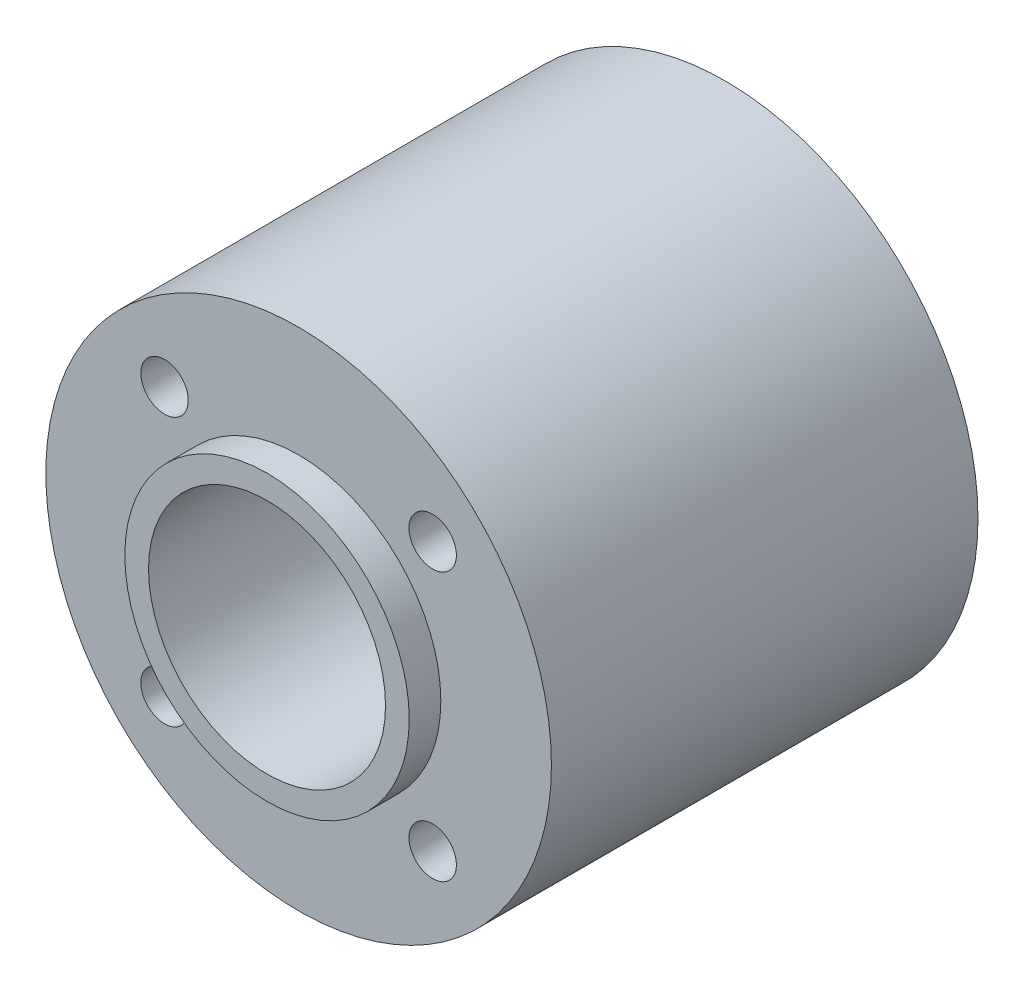
SolidWorks part; units mm, degrees
ref_plane "Plan de face" through (0, 0, 0) normal (0, 0, 1) x (1, 0, 0)
ref_plane "Plan de dessus" through (0, 0, 0) normal (0, 1, 0) x (1, 0, 0)
ref_plane "Plan de droite" through (0, 0, 0) normal (1, 0, 0) x (0, 0, -1)
sketch "Esquisse3" plane through (0, 0, 0) normal (0, 0, 1) x (1, 0, 0)
  circle A0 centre (0, 0) radius 7.5
  circle A1 centre (0, 0) radius 9
  circle A2 centre (0, 0) radius 16
  dimension "D1" = 32
  dimension "D2" = 18
  dimension "D3" = 15
extrude "Boss.-Extru.1" add sketch "Esquisse3" against normal blind 27 contours A2 A1 region at (-15.5475, 0, 0)
extrude "Boss.-Extru.2" add sketch "Esquisse3<3>" along normal blind 2 separate body contours A1 A0 region at (-8.7454, 0, 0)
sketch "Esquisse3<3>" plane through (0, 0, 0) normal (0, 0, 1) x (1, 0, 0) same geometry as "Esquisse3"
sketch "Esquisse5" plane through (0, 0, 2) normal (0, 0, 1) x (1, 0, 0)
  circle A0 centre (0, 0) radius 7.5 construction
  circle A1 centre (0, 0) radius 9
  circle A2 centre (0, 0) radius 9
  circle A3 centre (0, 0) radius 7.5
  dimension "D1" = 0
sketch "Esquisse7" plane through (0, 0, 0) normal (0, 0, -1) x (-1, 0, 0)
  circle A0 centre (0, 0) radius 7.5 construction
  circle A1 centre (0, 0) radius 9
  circle A2 centre (0, 0) radius 9
  circle A3 centre (0, 0) radius 7.5
  dimension "D1" = 0
extrude "Boss.-Extru.3" add sketch "Esquisse7" along normal blind 30
sketch "Esquisse8" plane through (0, 0, 0) normal (0, 0, 1) x (1, 0, 0)
  line L0 (0, 15.2709) -> (0, 0) construction
  line L1 (0, 0) -> (-12.0191, 12.0191) construction
  circle A0 centre (0, 0) radius 12 construction
  circle A1 centre (-8.4853, 8.4853) radius 1.5
  circle A2 centre (8.4853, 8.4853) radius 1.5
  dimension "D2" = 24
  dimension "D3" = 3
  dimension "D1" = 45
extrude "Enlèv. mat.-Extru.1" cut sketch "Esquisse8" against normal blind 30 contours A1 | A2 region at (-8.4853, 8.4853, 0)
mirror "Symétrie1" about plane through (0, 0, 0) normal (0, 1, 0) of "Enlèv. mat.-Extru.1"
